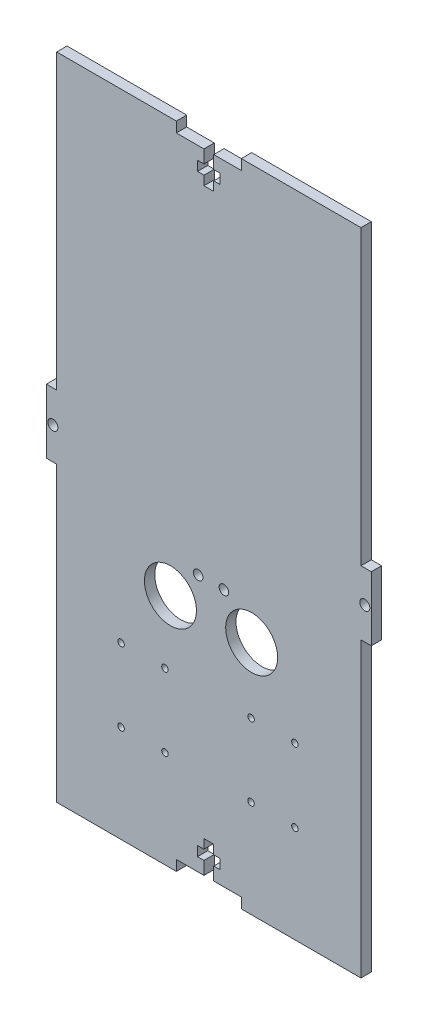
SolidWorks part; units mm, degrees
ref_plane "Front Plane" through (0, 0, 0) normal (0, 0, 1) x (1, 0, 0)
ref_plane "Top Plane" through (0, 0, 0) normal (0, 1, 0) x (1, 0, 0)
ref_plane "Right Plane" through (0, 0, 0) normal (1, 0, 0) x (0, 0, -1)
sketch "Sketch1" plane through (0, 0, 0) normal (0, 0, 1) x (1, 0, 0)
  line L0 (0.1756, 148.1163) -> (0.1756, -143.3274) construction
  line L5 (-50, -100) -> (50, 100) construction
  line L6 (-50, 100) -> (50, -100) construction
  line L7 (-100, 0) -> (100, 0) construction
  line L32 (-50, 100) -> (50, 100)
  line L35 (50, 100) -> (50, -100)
  line L36 (50, -100) -> (-50, -100)
  line L37 (-50, -100) -> (-50, 100)
  point P0 (0, 0)
  dimension "D1" = 100
  dimension "D2" = 200
extrude "Boss-Extrude2" add sketch "Sketch1" along normal blind 3.18
sketch "Sketch2" plane through (0, 0, 3.18) normal (0, 0, 1) x (1, 0, 0)
  line L0 (0, -100) -> (0, 100) construction
  line L1 (-123.0225, 0) -> (147.0753, 0) construction
  line L2 (50, 100) -> (-50, 100) construction
  line L4 (-10, 100) -> (-10, 96.82)
  line L5 (-10, 96.82) -> (-1.5, 96.82)
  line L6 (10, 100) -> (10, 96.82)
  line L7 (1.5, 96.82) -> (10, 96.82)
  line L9 (-1.5, 96.82) -> (-1.5, 92.82)
  line L10 (-1.5, 87) -> (1.5, 87)
  line L11 (1.5, 96.82) -> (1.5, 92.82)
  line L12 (-3.5, 92.82) -> (-1.5, 92.82)
  line L13 (-3.5, 92.82) -> (-3.5, 89.82)
  line L14 (-3.5, 89.82) -> (-1.5, 89.82)
  line L15 (3.5, 92.82) -> (3.5, 89.82)
  line L16 (1.5, 92.82) -> (3.5, 92.82)
  line L17 (-1.5, 89.82) -> (-1.5, 87)
  line L18 (1.5, 89.82) -> (1.5, 87)
  line L19 (1.5, 89.82) -> (3.5, 89.82)
  line L20 (-10, 100) -> (10, 100)
  line L21 (-50, -100) -> (50, -100) construction
  line L22 (-50, 100) -> (-50, -100) construction
  line L23 (-50, 9.875) -> (-46.82, 9.875)
  line L24 (-50, 9.875) -> (-50, 100)
  line L25 (-50, 100) -> (-46.82, 100)
  line L26 (-46.82, 9.875) -> (-46.82, 100)
  line L28 (-50, -9.875) -> (-46.82, -9.875)
  line L29 (-50, -9.875) -> (-50, -100)
  line L30 (-50, -100) -> (-46.82, -100)
  line L31 (-46.82, -9.875) -> (-46.82, -100)
  circle A0 centre (-48, 0) radius 1.55
  dimension "D11" = 3.1
  dimension "D12" = 2
  dimension "D1" = 4
  dimension "D2" = 3
  dimension "D3" = 3
  dimension "D4" = 20
  dimension "D5" = 7
  dimension "D6" = 3.18
  dimension "D7" = 13
  dimension "D8" = 19.75
  dimension "D9" = 3.18
  dimension "D10" = 3.18
extrude "Cut-Extrude1" cut sketch "Sketch2" against normal through all
mirror "Mirror1" about plane through (0, 0, 0) normal (0, 1, 0) of "Cut-Extrude1"
mirror "Mirror3" about plane through (0, 0, 0) normal (1, 0, 0) of "Cut-Extrude1"
sketch "Sketch4" plane through (0, 0, 0) normal (0, 0, -1) x (-1, 0, 0)
  circle A1 centre (13.5044, -70.05) radius 1
  circle A2 centre (13.5044, -70.05) radius 0.975 construction
  circle A3 centre (27.0044, -70.05) radius 1
  circle A7 centre (27.0044, -70.05) radius 0.975 construction
  circle A8 centre (27.0044, -47.59) radius 1
  circle A9 centre (27.0044, -47.59) radius 0.975 construction
  circle A10 centre (13.5044, -47.59) radius 1
  circle A11 centre (13.5044, -47.59) radius 0.975 construction
  circle A12 centre (-12.9956, -47.59) radius 1
  circle A13 centre (-26.4956, -47.59) radius 1
  circle A14 centre (-26.4956, -70.05) radius 1
  circle A15 centre (-12.9956, -70.05) radius 1
  circle A16 centre (-26.4956, -70.05) radius 0.975 construction
  circle A17 centre (-12.9956, -70.05) radius 0.975 construction
  circle A18 centre (-26.4956, -47.59) radius 0.975 construction
  circle A19 centre (-12.9956, -47.59) radius 0.975 construction
  dimension "D2" = 2
extrude "Cut-Extrude15" cut sketch "Sketch4" against normal blind 10
sketch "Sketch5" plane through (0, 0, 0) normal (0, 0, -1) x (-1, 0, 0)
  circle A0 centre (11.82, -27.4214) radius 8
  circle A1 centre (-13.18, -27.4214) radius 8
  circle A2 centre (11.82, -27.4214) radius 8 construction
  circle A3 centre (-13.18, -27.4214) radius 8 construction
  point P8 (55.3184, -40.3307)
  dimension "D1" = 16
extrude "Cut-Extrude16" cut sketch "Sketch5" against normal through all
sketch "Sketch6" plane through (0, 0, 0) normal (0, 0, -1) x (-1, 0, 0)
  circle A0 centre (3.2835, -17.6169) radius 1.47
  circle A2 centre (-4.6435, -17.6169) radius 1.47
  circle A3 centre (3.2835, -17.6169) radius 1.47 construction
  circle A4 centre (-4.6435, -17.6169) radius 1.47 construction
extrude "Cut-Extrude17" cut sketch "Sketch6" against normal through all
